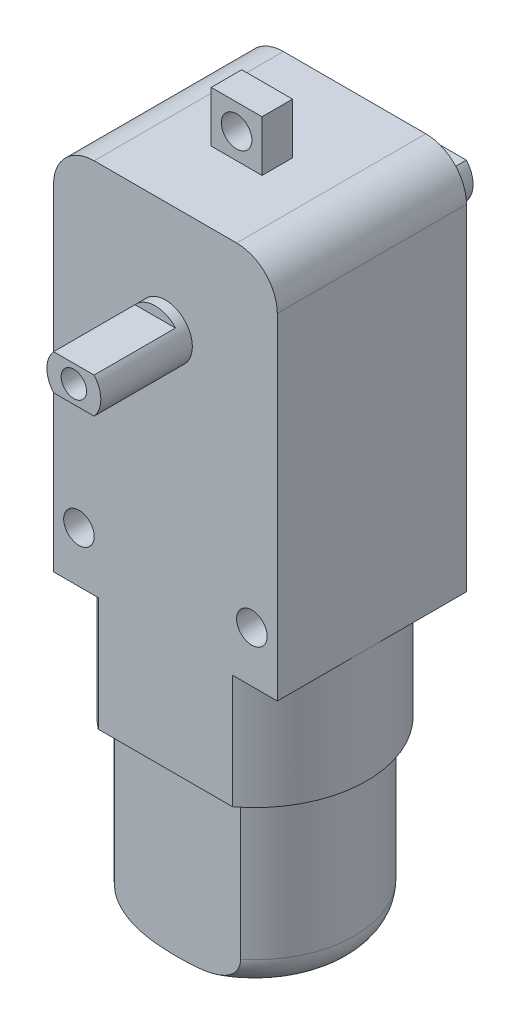
SolidWorks part; units mm, degrees
ref_plane "Front Plane" through (0, 0, 0) normal (0, 0, 1) x (1, 0, 0)
ref_plane "Top Plane" through (0, 0, 0) normal (0, 1, 0) x (1, 0, 0)
ref_plane "Right Plane" through (0, 0, 0) normal (1, 0, 0) x (0, 0, -1)
sketch "Sketch1" plane through (0, 0, 0) normal (0, 0, 1) x (1, 0, 0)
  line L1 (-11, 32.5) -> (11, 32.5)
  line L2 (-11, 32.5) -> (-11, -32.5)
  line L3 (-11, -32.5) -> (11, -32.5)
  line L4 (11, 32.5) -> (11, -32.5)
  line L5 (-11, 32.5) -> (11, -32.5) construction
  line L6 (-11, -32.5) -> (11, 32.5) construction
  point P0 (0, 0)
  dimension "D1" = 65
  dimension "D2" = 22
extrude "Boss-Extrude1" add sketch "Sketch1" along normal blind 18.6
fillet "Fillet1" radius 4 2 edges at (11, 32.5, 9.3) (-11, 32.5, 9.3)
sketch "Sketch2" plane through (0, 0, 18.6) normal (0, 0, 1) x (1, 0, 0)
  line L0 (0, 32.5) -> (0, 21.5) construction
  line L1 (7, 32.5) -> (-7, 32.5) construction
  circle A0 centre (0, 21.5) radius 2.65
  dimension "D1" = 5.3
  dimension "D2" = 11
extrude "Boss-Extrude2" add sketch "Sketch2" along normal blind 9 and the other way offset from surface (27.6 mm away) 9 other way up to face at (0, 9.7761, 0)
sketch "Sketch3" plane through (0, 0, 27.6) normal (0, 0, 1) x (1, 0, 0)
  line L0 (-1.99, 23.25) -> (1.99, 23.25)
  line L1 (0, 21.5) -> (0.866, 21.5) construction
  line L2 (-1.99, 19.75) -> (1.99, 19.75)
  arc A0 (1.99, 23.25) -> (-1.99, 23.25) centre (0, 21.5) ccw
  circle A1 centre (0, 21.5) radius 2.65
  arc A2 (-1.99, 19.75) -> (1.99, 19.75) centre (0, 21.5) ccw
  dimension "D2" = 3.5
  dimension "D1" = 0
extrude "Cut-Extrude1" cut sketch "Sketch3" against normal offset from surface (8 mm away) 1 up to face at (2.65, 21.5, 18.6)
sketch "Sketch4" plane through (0, 0, -9) normal (0, 0, -1) x (-1, 0, 0)
  line L0 (-1.99, 19.75) -> (1.99, 19.75) construction
  line L1 (1.99, 23.25) -> (-1.99, 23.25) construction
  line L2 (-1.99, 19.75) -> (1.99, 19.75)
  line L3 (1.99, 23.25) -> (-1.99, 23.25)
  arc A0 (-1.99, 19.75) -> (1.99, 19.75) centre (0, 21.5) ccw construction
  arc A1 (1.99, 23.25) -> (-1.99, 23.25) centre (0, 21.5) ccw construction
  arc A2 (-1.99, 19.75) -> (1.99, 19.75) centre (0, 21.5) ccw
  arc A3 (1.99, 23.25) -> (-1.99, 23.25) centre (0, 21.5) ccw
extrude "Cut-Extrude2" cut sketch "Sketch4" against normal offset from surface (8 mm away) 1 up to face at (2.65, 21.5, 0)
sketch "Sketch5" plane through (0, 0, -9) normal (0, 0, -1) x (-1, 0, 0)
  circle A0 centre (0, 21.5) radius 1.25
  dimension "D1" = 2.5
extrude "Cut-Extrude3" cut sketch "Sketch5" against normal through all
sketch "Sketch6" plane through (0, 0, 18.6) normal (0, 0, 1) x (1, 0, 0)
  line L0 (7, 32.5) -> (-7, 32.5) construction
  line L1 (-2.5, 37.5) -> (2.5, 37.5)
  line L2 (-2.5, 37.5) -> (-2.5, 27.5)
  line L3 (-2.5, 27.5) -> (2.5, 27.5)
  line L4 (2.5, 37.5) -> (2.5, 27.5)
  line L5 (-2.5, 37.5) -> (2.5, 27.5) construction
  line L6 (-2.5, 27.5) -> (2.5, 37.5) construction
  line L7 (0, 37.5) -> (0, 32.5) construction
  circle A0 centre (0, 35) radius 1.5
  point P0 (0, 32.5)
  dimension "D3" = 3
  dimension "D1" = 5
  dimension "D2" = 5
extrude "Boss-Extrude3" add sketch "Sketch6" against normal blind 3 from offset 7 offset against normal yes
sketch "Sketch7" plane through (0, 0, 0) normal (0, 0, -1) x (-1, 0, 0)
  circle A0 centre (0, 21.5) radius 2.65 construction
  circle A1 centre (0, 21.5) radius 2.65
  circle A2 centre (0, 21.5) radius 2.85
  dimension "D1" = 0.2
extrude "Boss-Extrude4" add sketch "Sketch7" along normal blind 0.5
sketch "Sketch8" plane through (0, 0, 0) normal (0, 0, -1) x (-1, 0, 0)
  line L0 (0, 0) -> (0, 21.5) construction
  circle A0 centre (0, 10.5) radius 2
  dimension "D1" = 4
  dimension "D2" = 11
extrude "Boss-Extrude5" add sketch "Sketch8" along normal blind 2
sketch "Sketch9" plane through (0, 0, 0) normal (0, 0, -1) x (-1, 0, 0)
  line L0 (-11, 0.5) -> (11, 0.5) construction
  line L1 (-11, -32.5) -> (-11, 28.5) construction
  line L2 (11, 28.5) -> (11, -32.5) construction
  line L3 (0, 0) -> (0, -4.264) construction
  line L4 (-7, 32.5) -> (7, 32.5) construction
  circle A0 centre (-8.5, 0.5) radius 1.5
  circle A1 centre (8.5, 0.5) radius 1.5
  dimension "D1" = 3
  dimension "D2" = 1
  dimension "D3" = 30.5
extrude "Cut-Extrude4" cut sketch "Sketch9" against normal through all
sketch "Sketch10" plane through (0, 0, 0) normal (0, 0, -1) x (-1, 0, 0)
  line L0 (-7, 32.5) -> (7, 32.5) construction
  line L1 (-13.6625, -36.1325) -> (14.0664, -36.1325)
  line L2 (-13.6625, -36.1325) -> (-13.6625, -4.5)
  line L3 (-13.6625, -4.5) -> (14.0664, -4.5)
  line L4 (14.0664, -36.1325) -> (14.0664, -4.5)
  dimension "D1" = 37
extrude "Cut-Extrude5" cut sketch "Sketch10" against normal blind 1
sketch "Sketch11" plane through (0, -32.5, 0) normal (0, -1, 0) x (1, 0, 0)
  line L0 (0, 18.6) -> (0, 1) construction
  line L1 (-11, 18.6) -> (11, 18.6) construction
  line L2 (-11, 1) -> (11, 1) construction
  circle A0 centre (0, 9.8) radius 11
  circle A1 centre (0, 9.8) radius 16.9967
extrude "Cut-Extrude6" cut sketch "Sketch11" against normal up to surface (28 mm away) up to face at (0, -4.5, 0.5)
sketch "Sketch12" plane through (0, -32.5, 0) normal (0, -1, 0) x (1, 0, 0)
  line L0 (6.1871, 17.4) -> (-6.1871, 17.4)
  line L1 (-6.1871, 2.2) -> (6.1871, 2.2)
  line L2 (6.6, 18.6) -> (-6.6, 18.6)
  line L3 (-6.6, 1) -> (6.6, 1)
  line L4 (6.6, 18.6) -> (-6.6, 18.6)
  line L5 (-6.6, 1) -> (6.6, 1)
  arc A0 (6.1871, 2.2) -> (6.1871, 17.4) centre (0, 9.8) ccw
  arc A1 (-6.1871, 17.4) -> (-6.1871, 2.2) centre (0, 9.8) ccw
  arc A2 (6.6, 1) -> (6.6, 18.6) centre (0, 9.8) ccw
  arc A3 (-6.6, 18.6) -> (-6.6, 1) centre (0, 9.8) ccw
  arc A4 (6.6, 1) -> (6.6, 18.6) centre (0, 9.8) ccw
  arc A5 (-6.6, 18.6) -> (-6.6, 1) centre (0, 9.8) ccw
  dimension "D1" = 0
  dimension "D2" = 1.2
extrude "Cut-Extrude7" cut sketch "Sketch12" against normal offset from surface (16.8 mm away) 11.2 up to face at (-9.8796, -4.5, 15.8398)
fillet "Fillet2" radius 3 1 edges at (-9.8, -32.5, 9.8)
